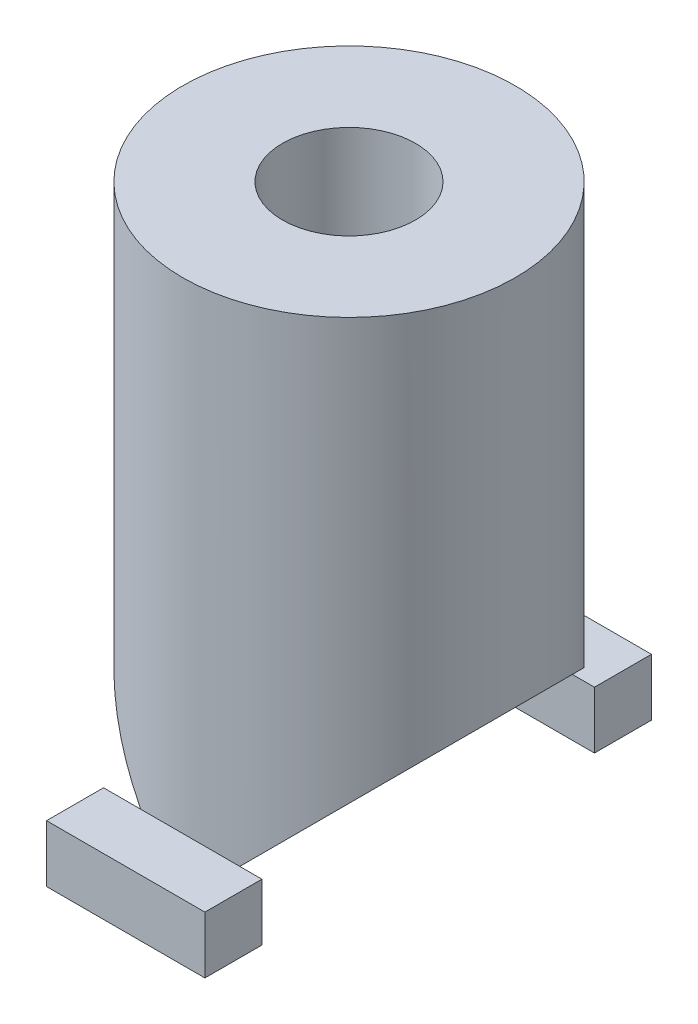
SolidWorks part; units mm, degrees
ref_plane "Front Plane" through (0, 0, 0) normal (0, 0, 1) x (1, 0, 0)
ref_plane "Top Plane" through (0, 0, 0) normal (0, 1, 0) x (1, 0, 0)
ref_plane "Right Plane" through (0, 0, 0) normal (1, 0, 0) x (0, 0, -1)
sketch "Sketch2" plane through (0, 0, 0) normal (0, 1, 0) x (1, 0, 0)
  line L0 (0, -55) -> (0, 55) construction
  circle A1 centre (0, 0) radius 5.25
  dimension "D1" = 10.5
extrude "Boss-Extrude1" add sketch "Sketch2" along normal blind 17
sketch "Sketch3" plane through (0, 17, 0) normal (0, 1, 0) x (1, 0, 0)
  circle A0 centre (0, 0) radius 2.1
  dimension "D1" = 4.2
extrude "Cut-Extrude1" cut sketch "Sketch3" against normal blind 7
sketch "Sketch4" plane through (0, 0, 0) normal (1, 0, 0) x (0, 0, -1)
  circle A0 centre (0, 0) radius 5.25
  dimension "D1" = 10.5
extrude "Cut-Extrude3" cut sketch "Sketch4" against normal blind 7 and the other way blind 7
sketch "Sketch5" plane through (0, 0, 0) normal (1, 0, 0) x (0, 0, -1)
  line L0 (5.25, 1.8021) -> (5.25, 0)
  line L1 (-7.05, 0) -> (-5.25, 0)
  line L2 (5.25, 0) -> (5.25, 17) construction
  line L3 (5.25, 1.8021) -> (7.05, 1.8021)
  line L4 (7.05, 1.8021) -> (7.05, 0)
  line L5 (7.05, 0) -> (5.25, 0)
  line L6 (-7.05, 1.8021) -> (-7.05, 0)
  line L7 (-5.25, 1.8021) -> (-7.05, 1.8021)
  line L8 (-5.25, 1.8021) -> (-5.25, 0)
  dimension "D2" = 1.8
  dimension "D3" = 1.8021
extrude "Boss-Extrude2" add sketch "Sketch5" along normal blind 2.5 and the other way blind 2.5 separate body
